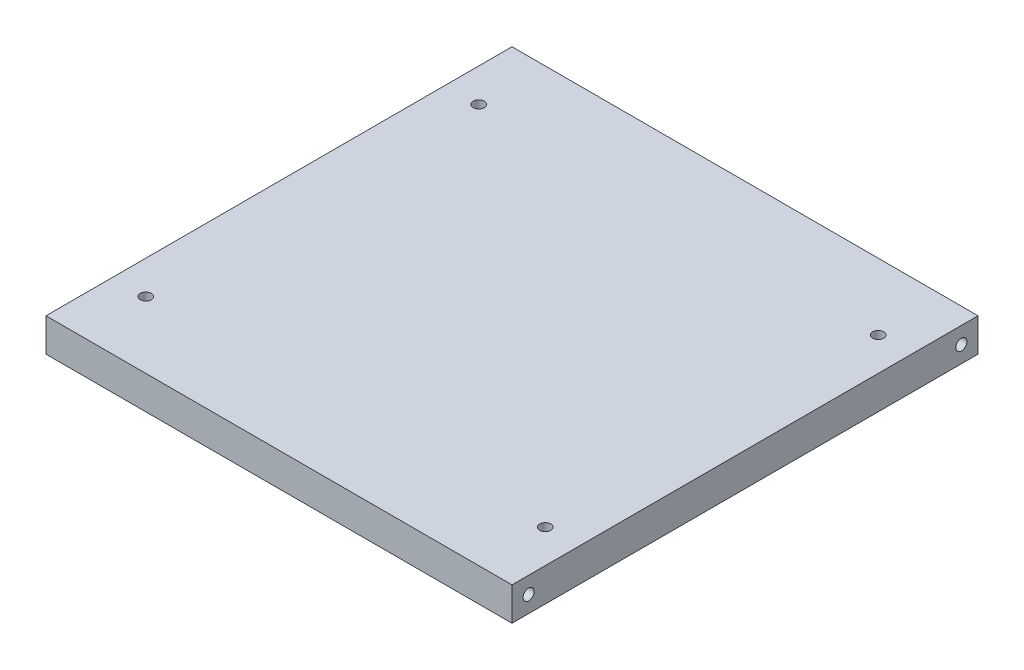
SolidWorks part; units mm, degrees
material "AISI 1020"
ref_plane "Front Plane" through (0, 0, 0) normal (0, 0, 1) x (1, 0, 0)
ref_plane "Top Plane" through (0, 0, 0) normal (0, 1, 0) x (1, 0, 0)
ref_plane "Right Plane" through (0, 0, 0) normal (1, 0, 0) x (0, 0, -1)
sketch "Sketch1" plane through (0, 0, 0) normal (0, 1, 0) x (1, 0, 0)
  line L1 (0, 0) -> (84, 0)
  line L2 (0, 0) -> (0, 84)
  line L3 (0, 84) -> (84, 84)
  line L4 (84, 0) -> (84, 84)
  dimension "D1" = 84
  dimension "D2" = 84
extrude "Boss-Extrude1" add sketch "Sketch1" along normal blind 6
sketch "Sketch2" plane through (0, 6, 0) normal (0, 1, 0) x (1, 0, 0)
  line L0 (84, 84) -> (0, 84) construction
  line L1 (0, 84) -> (0, 0) construction
  circle A0 centre (6, 72) radius 1
  dimension "D1" = 2
  dimension "D3" = 6
  dimension "D2" = 12
extrude "Cut-Extrude1" cut sketch "Sketch2" against normal blind 6
pattern_linear "LPattern1" count 2 spacing 72 along (1, 0, 0) count 2 spacing 60 along (0, 0, 1) of "Cut-Extrude1"
sketch "Sketch3" plane through (0, 0, 0) normal (-1, 0, 0) x (0, 0, 1)
  line L0 (-84, 3) -> (-3, 3) construction
  line L1 (-84, 6) -> (-84, 0) construction
  line L2 (0, 6) -> (0, 0) construction
  circle A0 centre (-81, 3) radius 1
  circle A1 centre (-3, 3) radius 1
  dimension "D1" = 3
  dimension "D3" = 2
  dimension "D4" = 2
  dimension "D2" = 3
extrude "Cut-Extrude2" cut sketch "Sketch3" against normal blind 10
ref_plane "Plane1" through (42, 0, 0) normal (-1, 0, 0) x (0, 0, 1)
mirror "Mirror1" about plane through (42, 0, 0) normal (-1, 0, 0) of "Cut-Extrude2"
